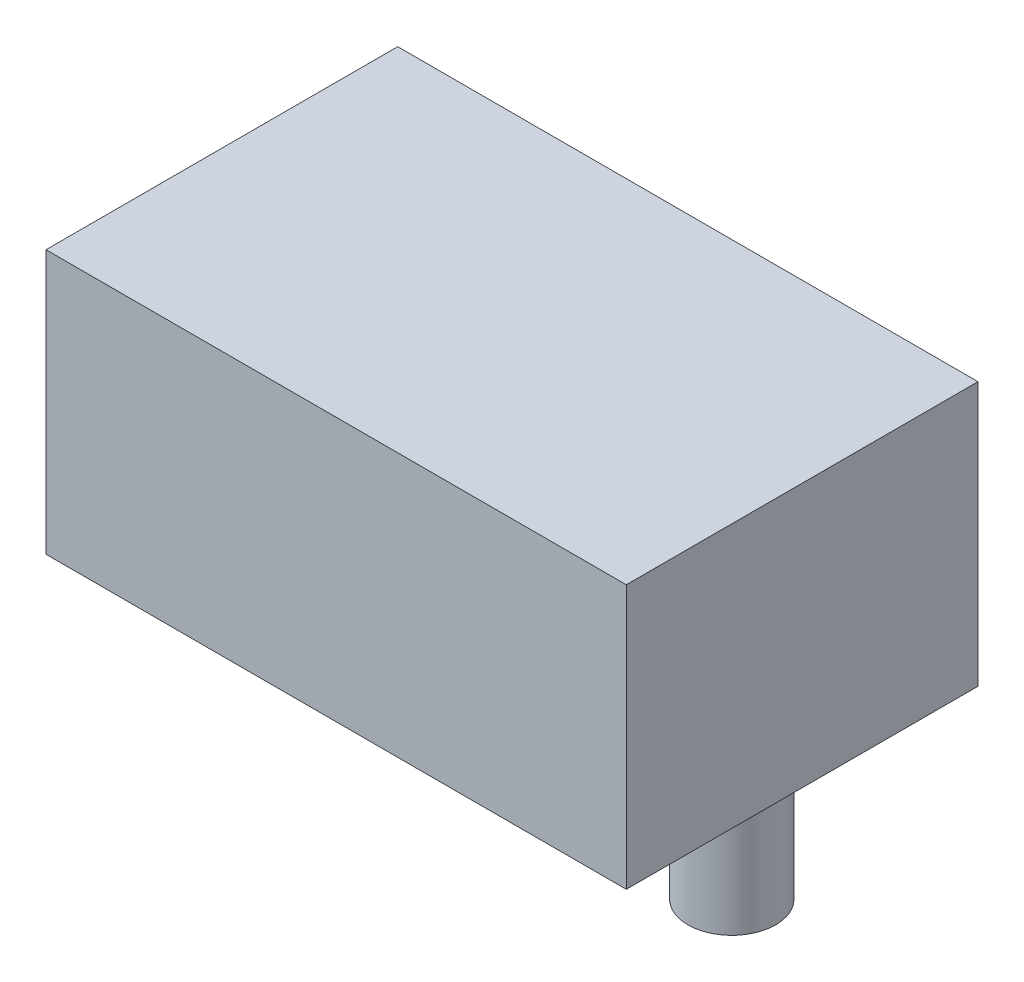
SolidWorks part; units mm, degrees
ref_plane "Front Plane" through (0, 0, 0) normal (0, 0, 1) x (1, 0, 0)
ref_plane "Top Plane" through (0, 0, 0) normal (0, 1, 0) x (1, 0, 0)
ref_plane "Right Plane" through (0, 0, 0) normal (1, 0, 0) x (0, 0, -1)
sketch "Sketch1" plane through (0, 0, 0) normal (0, 1, 0) x (1, 0, 0)
  line L7 (-20.955, 12.7) -> (20.955, 12.7)
  line L8 (-20.955, 12.7) -> (-20.955, -12.7)
  line L9 (-20.955, -12.7) -> (20.955, -12.7)
  line L10 (20.955, 12.7) -> (20.955, -12.7)
  circle A0 centre (0, 0) radius 6.2865
  circle A1 centre (-15.875, 0) radius 3.175
  circle A2 centre (15.875, 0) radius 3.175
  point P4 (0, -12.7)
  point P5 (-20.955, 0)
  dimension "D1" = 12.573
  dimension "D4" = 6.35
  dimension "D2" = 25.4
  dimension "D3" = 41.91
  dimension "D5" = 15.875
  dimension "D6" = 15.875
extrude "Boss-Extrude1" add sketch "Sketch1" along normal blind 19.05 contours L10 L7 L8 L9 A2 A1 | A1 | A2 | A0 region at (0, 0, -12.2099) region at (0, 0, 0) region at (-15.875, 0, 0) region at (15.875, 0, 0)
extrude "Cut-Extrude1" cut sketch "Sketch1<4>" along normal blind 9.525 contours A0
sketch "Sketch1<4>" plane through (0, 0, 0) normal (0, 1, 0) x (1, 0, 0) same geometry as "Sketch1"
extrude "Boss-Extrude2" add sketch "Sketch1<5>" against normal blind 9.525 contours A2 | A1
sketch "Sketch1<5>" plane through (0, 0, 0) normal (0, 1, 0) x (1, 0, 0) same geometry as "Sketch1"
